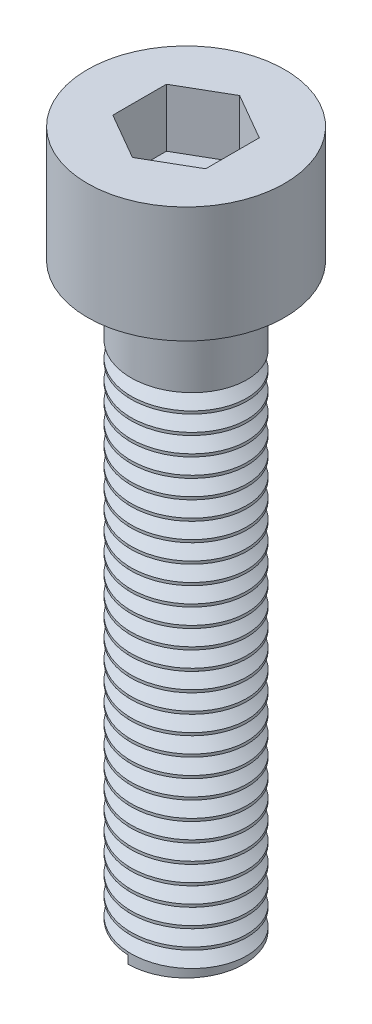
SolidWorks part; units mm, degrees
material "Acero aleado"
ref_plane "Alzado" through (0, 0, 0) normal (0, 0, 1) x (1, 0, 0)
ref_plane "Planta" through (0, 0, 0) normal (0, 1, 0) x (1, 0, 0)
ref_plane "Vista lateral" through (0, 0, 0) normal (1, 0, 0) x (0, 0, -1)
sketch "Sk_Cabeza" plane through (0, 0, 0) normal (0, 1, 0) x (1, 0, 0)
  circle A0 centre (0, 0) radius 4.25
  dimension "DIAM1" = 8.5
extrude "Cabeza" add sketch "Sk_Cabeza" along normal blind 5 from offset 0
sketch "Sk_Cana" plane through (0, 0, 0) normal (0, 1, 0) x (1, 0, 0)
  circle A0 centre (0, 0) radius 2.5
  dimension "DIAM2" = 5
extrude "Cana" add sketch "Sk_Cana" along normal blind 25 from offset 25 offset against normal yes
ref_plane "Plano_cabeza" through (0, 5, 0) normal (0, 1, 0) x (1, 0, 0)
sketch "Sk_Hueco_Allen" plane through (0, 5, 0) normal (0, 1, 0) x (1, 0, 0)
  line L0 (2, -1.1547) -> (0, -2.3094)
  line L1 (0, -2.3094) -> (-2, -1.1547)
  line L2 (-2, -1.1547) -> (-2, 1.1547)
  line L3 (-2, 1.1547) -> (0, 2.3094)
  line L4 (0, 2.3094) -> (2, 1.1547)
  line L5 (2, 1.1547) -> (2, -1.1547)
extrude "Hueco_Allen" cut sketch "Sk_Hueco_Allen" against normal blind 2.5
ref_plane "Plano_punta" through (0, -25, 0) normal (0, 1, 0) x (1, 0, 0)
sketch "Sk_Helice" plane through (0, -25, 0) normal (0, 1, 0) x (1, 0, 0)
  circle A0 centre (0, 0) radius 2.5
curve "Helice_rosca" pitch 0.8 height 22 radius 2.5 left hand yes centre (0, -25, 0) axis (0, 1, 0) start towards (0, 0, 1)
sketch "Sk_Perfil_rosca" plane through (0, 0, 0) normal (1, 0, 0) x (0, 0, -1)
  line L0 (-2.7, -25.48) -> (-2.0093, -25)
  line L1 (-2.0093, -25) -> (-2.7, -24.52)
  line L2 (-2.7, -24.52) -> (-2.7, -25.48)
sweep "Rosca_M5x0,8" cut profiles "Sk_Perfil_rosca" path "Helice_rosca"
